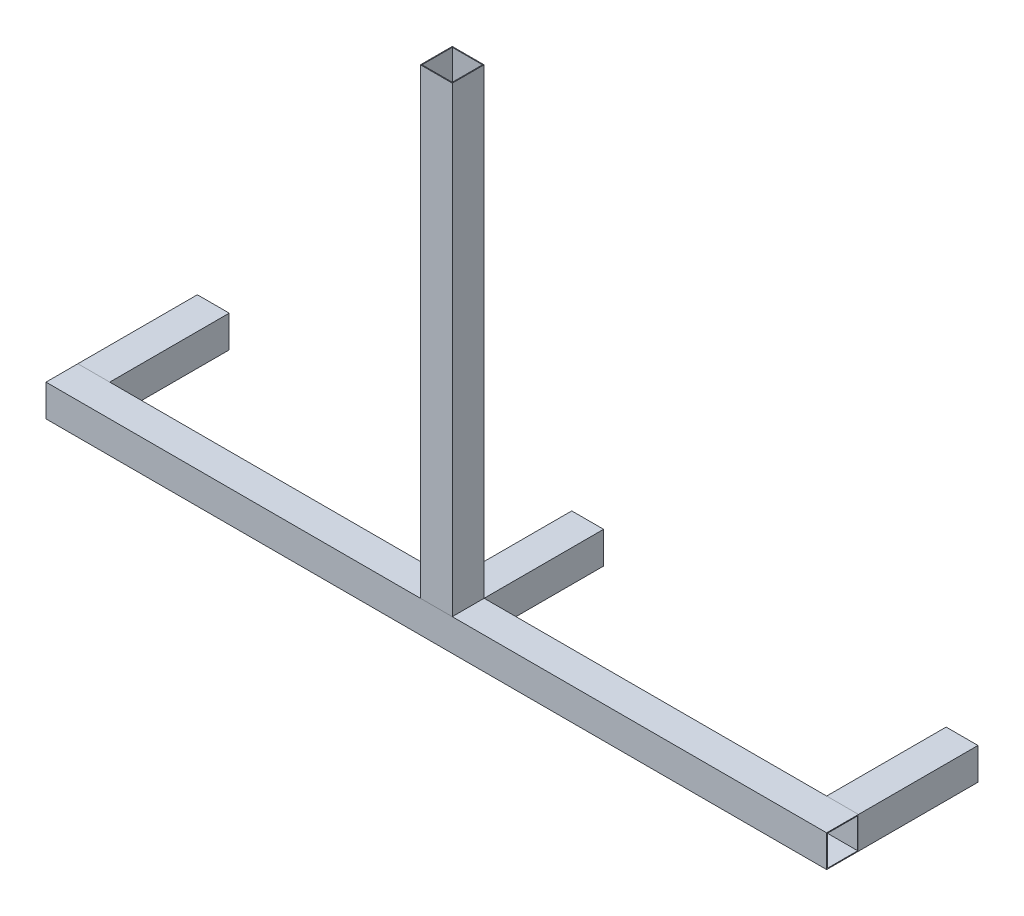
SolidWorks part; units mm, degrees
ref_plane "Alzado" through (0, 0, 0) normal (0, 0, 1) x (1, 0, 0)
ref_plane "Planta" through (0, 0, 0) normal (0, 1, 0) x (1, 0, 0)
ref_plane "Vista lateral" through (0, 0, 0) normal (1, 0, 0) x (0, 0, -1)
sketch "Croquis1" plane through (0, 0, 0) normal (1, 0, 0) x (0, 0, -1)
  line L1 (20, -20) -> (-20, -20)
  line L2 (20, -20) -> (20, 20)
  line L3 (20, 20) -> (-20, 20)
  line L4 (-20, -20) -> (-20, 20)
  line L5 (20, -20) -> (-20, 20) construction
  line L6 (20, 20) -> (-20, -20) construction
  point P0 (0, 0)
  dimension "D1" = 40
extrude "Extruir-Lámina1" add sketch "Croquis1" along normal mid plane 980 thin thin type one direction reverse wall 1
sketch "Croquis2" plane through (0, 0, -20) normal (0, 0, -1) x (-1, 0, 0)
  line L1 (20, -20) -> (-20, -20)
  line L2 (20, -20) -> (20, 20)
  line L3 (20, 20) -> (-20, 20)
  line L4 (-20, -20) -> (-20, 20)
  line L5 (20, -20) -> (-20, 20) construction
  line L6 (20, 20) -> (-20, -20) construction
  line L7 (-490, -20) -> (-490, 20) construction
  line L8 (-490, 20) -> (490, 20) construction
  circle A0 centre (0, 0) radius 28.2843 construction
  point P0 (0, 0)
extrude "Extruir-Lámina3" add sketch "Croquis2" along normal blind 150 separate body thin thin type one direction reverse wall 1
sketch "Croquis3" plane through (0, 0, -20) normal (0, 0, -1) x (-1, 0, 0)
  line L0 (-490, -20) -> (490, -20) construction
  line L1 (-490, 20) -> (-450, 20)
  line L2 (-490, 20) -> (-490, -20)
  line L3 (-490, -20) -> (-450, -20)
  line L4 (-450, 20) -> (-450, -20)
  line L5 (450, 20) -> (490, -20) construction
  line L6 (490, 20) -> (450, 20)
  line L7 (490, 20) -> (490, -20)
  line L8 (490, -20) -> (450, -20)
  line L9 (450, 20) -> (450, -20)
  line L10 (-490, 20) -> (-450, -20) construction
  line L11 (-490, 20) -> (490, 20) construction
  circle A0 centre (470, 0) radius 27.5772 construction
  circle A1 centre (-470, 0) radius 28.2843 construction
extrude "Extruir-Lámina5" add sketch "Croquis3" along normal blind 150 separate body thin thin type one direction reverse wall 1
sketch "Croquis4" plane through (0, 20, 0) normal (0, 1, 0) x (1, 0, 0)
  line L1 (20, -20) -> (-20, -20)
  line L2 (20, -20) -> (20, 20)
  line L3 (20, 20) -> (-20, 20)
  line L4 (-20, -20) -> (-20, 20)
  line L5 (20, -20) -> (-20, 20) construction
  line L6 (20, 20) -> (-20, -20) construction
  circle A0 centre (0, 0) radius 28.2843 construction
  point P0 (0, 0)
extrude "Extruir-Lámina6" add sketch "Croquis4" along normal blind 580 separate body thin thin type one direction reverse wall 1
